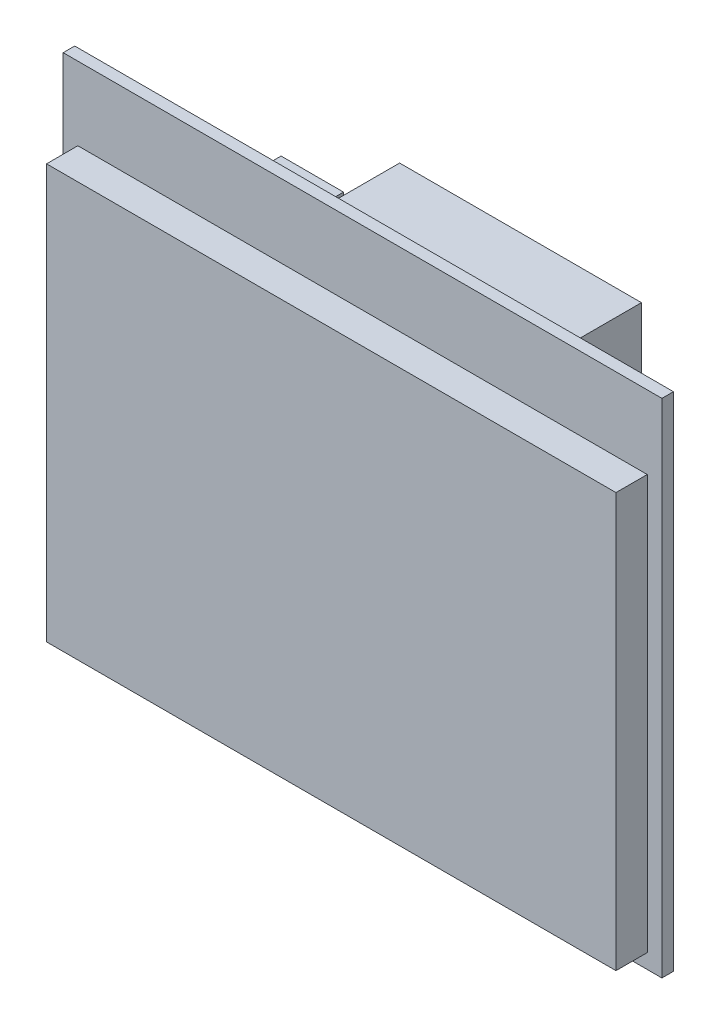
SolidWorks part; units mm, degrees
ref_plane "Front Plane" through (0, 0, 0) normal (0, 0, 1) x (1, 0, 0)
ref_plane "Top Plane" through (0, 0, 0) normal (0, 1, 0) x (1, 0, 0)
ref_plane "Right Plane" through (0, 0, 0) normal (1, 0, 0) x (0, 0, -1)
sketch "Sketch1" plane through (0, 0, 0) normal (0, 0, 1) x (1, 0, 0)
  line L1 (-32.25, -24.25) -> (32.25, -24.25) construction
  line L2 (-32.25, -24.25) -> (-32.25, 24.25) construction
  line L3 (-32.25, 24.25) -> (32.25, 24.25) construction
  line L4 (32.25, -24.25) -> (32.25, 24.25) construction
  line L5 (-32.25, -24.25) -> (32.25, 24.25) construction
  line L6 (-32.25, 24.25) -> (32.25, -24.25) construction
  line L7 (-36, 28) -> (41.7, 28) construction
  line L8 (-36, 28) -> (-36, -28.5) construction
  line L9 (-36, -28.5) -> (41.7, -28.5) construction
  line L10 (41.7, 28) -> (41.7, -28.5) construction
  line L11 (-38, 38) -> (43.7, 38)
  line L12 (-38, 38) -> (-38, -30.5)
  line L13 (-38, -30.5) -> (43.7, -30.5)
  line L14 (43.7, 38) -> (43.7, -30.5)
  point P0 (0, 0)
  dimension "D1" = 64.5
  dimension "D2" = 48.5
  dimension "D3" = 3.75
  dimension "D4" = 3.75
  dimension "D5" = 56.5
  dimension "D6" = 77.7
  dimension "D7" = 2
  dimension "D8" = 2
  dimension "D9" = 2
  dimension "D10" = 10
extrude "Boss-Extrude1" add sketch "Sketch1" along normal blind 1.5748
sketch "Sketch2" plane through (0, 0, 1.5748) normal (0, 0, 1) x (1, 0, 0)
  line L1 (-36, -28.5) -> (41.7, -28.5)
  line L2 (-36, -28.5) -> (-36, 28)
  line L3 (-36, 28) -> (41.7, 28)
  line L4 (41.7, -28.5) -> (41.7, 28)
  line L5 (41.7, 28) -> (49.6841, 28) construction
  line L6 (-36, 28) -> (-43.9841, 28) construction
  line L10 (-32.25, -24.25) -> (32.25, -24.25) construction
  line L11 (-32.25, -24.25) -> (-32.25, 24.25) construction
  line L12 (-32.25, 24.25) -> (32.25, 24.25) construction
  line L13 (32.25, -24.25) -> (32.25, 24.25) construction
  line L14 (-32.25, -24.25) -> (32.25, 24.25) construction
  line L15 (-32.25, 24.25) -> (32.25, -24.25) construction
  point P0 (0, 0)
  point P14 (0, 0)
  point P19 (-83.1395, 7.4926)
  dimension "D1" = 56.5
  dimension "D2" = 77.7
  dimension "D3" = 3.75
  dimension "D4" = 48.5
  dimension "D5" = 64.5
  dimension "D6" = 3.75
extrude "Boss-Extrude2" add sketch "Sketch2" along normal blind 4.27
sketch "Sketch3" plane through (0, 0, 0) normal (0, 0, -1) x (-1, 0, 0)
  line L1 (2.5361, 37.4679) -> (-30.4639, 37.4679)
  line L2 (2.5361, 37.4679) -> (2.5361, 28.5079)
  line L3 (2.5361, 28.5079) -> (-30.4639, 28.5079)
  line L4 (-30.4639, 37.4679) -> (-30.4639, 28.5079)
  dimension "D1" = 8.96
  dimension "D2" = 33
extrude "Boss-Extrude3" add sketch "Sketch3" along normal blind 8.87
sketch "Sketch4" plane through (0, 0, 0) normal (0, 0, -1) x (-1, 0, 0)
  line L1 (5.3161, 35.0775) -> (13.8411, 35.0775)
  line L2 (5.3161, 35.0775) -> (5.3161, 29.8525)
  line L3 (5.3161, 29.8525) -> (13.8411, 29.8525)
  line L4 (13.8411, 35.0775) -> (13.8411, 29.8525)
  line L6 (2.5361, 28.5079) -> (2.5361, 37.4679) construction
  dimension "D1" = 5.225
  dimension "D2" = 8.525
  dimension "D4" = 2.78
extrude "Boss-Extrude4" add sketch "Sketch4" along normal blind 4
